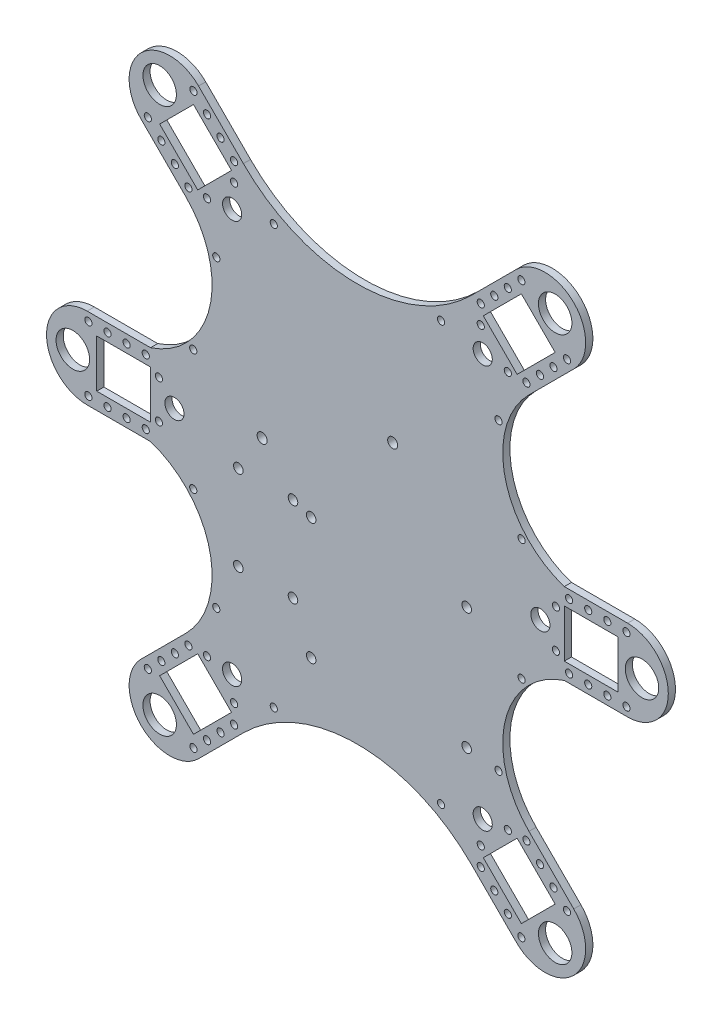
SolidWorks part; units mm, degrees
ref_plane "Płaszczyzna przednia" through (0, 0, 0) normal (0, 0, 1) x (1, 0, 0)
ref_plane "Płaszczyzna górna" through (0, 0, 0) normal (0, 1, 0) x (1, 0, 0)
ref_plane "Płaszczyzna prawa" through (0, 0, 0) normal (1, 0, 0) x (0, 0, -1)
sketch "Model" plane through (0, 0, 0) normal (0, 0, 1) x (1, 0, 0)
  line L0 (2252.0948, 928.366) -> (2233.3565, 947.1043)
  line L1 (2209.3149, 923.0627) -> (2228.0532, 904.3244)
  line L2 (2247.1451, 923.4163) -> (2231.2352, 939.3262)
  line L3 (2233.0029, 909.2741) -> (2247.1451, 923.4163)
  line L4 (2217.093, 925.184) -> (2233.0029, 909.2741)
  line L5 (2231.2352, 939.3262) -> (2217.093, 925.184)
  line L6 (2213.2789, 842.2855) -> (2186.7789, 842.2855)
  line L7 (2186.7789, 808.2855) -> (2213.2789, 808.2855)
  line L8 (2213.2789, 835.2855) -> (2190.7789, 835.2855)
  line L9 (2213.2789, 815.2855) -> (2213.2789, 835.2855)
  line L10 (2190.7789, 815.2855) -> (2213.2789, 815.2855)
  line L11 (2190.7789, 835.2855) -> (2190.7789, 815.2855)
  line L12 (2231.2352, 711.2448) -> (2217.093, 725.3869)
  line L13 (2217.093, 725.3869) -> (2233.0029, 741.2968)
  line L14 (2233.0029, 741.2968) -> (2247.1451, 727.1547)
  line L15 (2247.1451, 727.1547) -> (2231.2352, 711.2448)
  line L16 (2209.3149, 727.5082) -> (2228.0532, 746.2466)
  line L17 (2252.0948, 722.2049) -> (2233.3565, 703.4666)
  line L18 (2347.4886, 722.2049) -> (2366.2269, 703.4666)
  line L19 (2390.2686, 727.5082) -> (2371.5302, 746.2466)
  line L20 (2352.4384, 727.1547) -> (2368.3483, 711.2448)
  line L21 (2366.5805, 741.2968) -> (2352.4384, 727.1547)
  line L22 (2382.4904, 725.3869) -> (2366.5805, 741.2968)
  line L23 (2368.3483, 711.2448) -> (2382.4904, 725.3869)
  line L24 (2408.8046, 835.2855) -> (2408.8046, 815.2855)
  line L25 (2149.0438, 825.2855) -> (2452.6529, 825.2855) construction
  line L26 (2408.8046, 815.2855) -> (2386.3046, 815.2855)
  line L27 (2386.3046, 815.2855) -> (2386.3046, 835.2855)
  line L28 (2386.3046, 835.2855) -> (2408.8046, 835.2855)
  line L29 (2412.8046, 808.2855) -> (2386.3046, 808.2855)
  line L30 (2386.3046, 842.2855) -> (2412.8046, 842.2855)
  line L31 (2368.3483, 939.3262) -> (2382.4904, 925.184)
  line L32 (2382.4904, 925.184) -> (2366.5805, 909.2741)
  line L33 (2366.5805, 909.2741) -> (2352.4384, 923.4163)
  line L34 (2352.4384, 923.4163) -> (2368.3483, 939.3262)
  line L35 (2390.2686, 923.0627) -> (2371.5302, 904.3244)
  line L36 (2347.4886, 928.366) -> (2366.2269, 947.1043)
  line L39 (2201.5792, 877.8504) -> (2238.0005, 869.1768) construction
  line L66 (2299.7917, 657.0048) -> (2299.7917, 965.92) construction
  arc A2 (2209.3149, 727.5082) -> (2233.3565, 703.4666) centre (2221.3357, 715.4874) ccw
  arc A3 (2252.0948, 928.366) -> (2347.4886, 928.366) centre (2299.7917, 976.0629) ccw
  circle A4 centre (2242.5489, 717.6087) radius 1.5
  circle A5 centre (2248.2057, 927.3054) radius 1.5
  circle A6 centre (2248.2057, 919.5272) radius 1.5
  arc A7 (2228.0532, 904.3244) -> (2213.2789, 842.2855) centre (2201.5792, 877.8504) cw
  circle A8 centre (2229.1139, 908.2135) radius 1.5
  circle A9 centre (2223.457, 913.8703) radius 1.5
  circle A10 centre (2217.8001, 919.5272) radius 1.5
  circle A11 centre (2212.1433, 925.184) radius 1.5
  circle A12 centre (2217.093, 939.3262) radius 7
  circle A13 centre (2236.892, 908.2135) radius 1.5
  circle A14 centre (2231.2352, 944.2759) radius 1.5
  circle A15 centre (2236.892, 938.6191) radius 1.5
  circle A16 centre (2242.5489, 932.9622) radius 1.5
  arc A17 (2209.3149, 923.0627) -> (2233.3565, 947.1043) centre (2221.3357, 935.0835) cw
  circle A18 centre (2236.892, 711.9519) radius 1.5
  circle A19 centre (2180.7789, 825.2855) radius 7
  circle A20 centre (2187.2789, 838.7855) radius 1.5
  circle A21 centre (2195.2789, 838.7855) radius 1.5
  circle A22 centre (2203.2789, 838.7855) radius 1.5
  circle A23 centre (2187.2789, 811.7855) radius 1.5
  circle A24 centre (2195.2789, 811.7855) radius 1.5
  circle A25 centre (2203.2789, 811.7855) radius 1.5
  circle A26 centre (2211.2789, 811.7855) radius 1.5
  circle A27 centre (2216.7789, 817.2855) radius 1.5
  circle A28 centre (2211.2789, 838.7855) radius 1.5
  circle A29 centre (2216.7789, 833.2855) radius 1.5
  arc A30 (2186.7789, 808.2855) -> (2186.7789, 842.2855) centre (2186.7789, 825.2855) cw
  circle A31 centre (2231.2352, 706.295) radius 1.5
  circle A32 centre (2236.892, 742.3575) radius 1.5
  circle A33 centre (2217.093, 711.2448) radius 7
  circle A34 centre (2212.1433, 725.3869) radius 1.5
  circle A35 centre (2217.8001, 731.0438) radius 1.5
  circle A36 centre (2223.457, 736.7006) radius 1.5
  circle A37 centre (2229.1139, 742.3575) radius 1.5
  arc A38 (2228.0532, 746.2466) -> (2213.2789, 808.2855) centre (2201.5792, 772.7206) ccw
  circle A39 centre (2248.2057, 731.0438) radius 1.5
  circle A42 centre (2248.2057, 723.2656) radius 1.5
  arc A43 (2252.0948, 722.2049) -> (2347.4886, 722.2049) centre (2299.7917, 674.508) cw
  circle A45 centre (2351.3777, 723.2656) radius 1.5
  circle A48 centre (2351.3777, 731.0438) radius 1.5
  arc A49 (2371.5302, 746.2466) -> (2386.3046, 808.2855) centre (2398.0042, 772.7206) cw
  circle A50 centre (2370.4696, 742.3575) radius 1.5
  circle A51 centre (2376.1264, 736.7006) radius 1.5
  circle A52 centre (2381.7833, 731.0438) radius 1.5
  circle A53 centre (2387.4401, 725.3869) radius 1.5
  circle A54 centre (2382.4904, 711.2448) radius 7
  circle A55 centre (2362.6914, 742.3575) radius 1.5
  circle A56 centre (2368.3483, 706.295) radius 1.5
  arc A57 (2412.8046, 808.2855) -> (2412.8046, 842.2855) centre (2412.8046, 825.2855) ccw
  circle A58 centre (2382.8046, 833.2855) radius 1.5
  circle A59 centre (2388.3046, 838.7855) radius 1.5
  circle A60 centre (2382.8046, 817.2855) radius 1.5
  circle A61 centre (2388.3046, 811.7855) radius 1.5
  circle A62 centre (2396.3046, 811.7855) radius 1.5
  circle A63 centre (2404.3046, 811.7855) radius 1.5
  circle A64 centre (2412.3046, 811.7855) radius 1.5
  circle A65 centre (2396.3046, 838.7855) radius 1.5
  circle A66 centre (2404.3046, 838.7855) radius 1.5
  circle A67 centre (2412.3046, 838.7855) radius 1.5
  circle A68 centre (2418.8046, 825.2855) radius 7
  circle A69 centre (2362.6914, 711.9519) radius 1.5
  arc A70 (2390.2686, 923.0627) -> (2366.2269, 947.1043) centre (2378.2478, 935.0835) ccw
  circle A71 centre (2357.0346, 932.9622) radius 1.5
  circle A72 centre (2362.6914, 938.6191) radius 1.5
  circle A73 centre (2368.3483, 944.2759) radius 1.5
  circle A74 centre (2362.6914, 908.2135) radius 1.5
  circle A75 centre (2382.4904, 939.3262) radius 7
  circle A76 centre (2387.4401, 925.184) radius 1.5
  circle A77 centre (2381.7833, 919.5272) radius 1.5
  circle A78 centre (2376.1264, 913.8703) radius 1.5
  circle A79 centre (2370.4696, 908.2135) radius 1.5
  arc A81 (2371.5302, 904.3244) -> (2386.3046, 842.2855) centre (2398.0042, 877.8504) ccw
  circle A82 centre (2351.3777, 919.5272) radius 1.5
  circle A83 centre (2351.3777, 927.3054) radius 1.5
  circle A84 centre (2357.0346, 717.6087) radius 1.5
  arc A85 (2390.2686, 727.5082) -> (2366.2269, 703.4666) centre (2378.2478, 715.4874) cw
  circle A90 centre (2345.4797, 814.428) radius 2
  circle A91 centre (2345.4797, 763.588) radius 2
  circle A92 centre (2280.4557, 763.588) radius 2
  circle A93 centre (2280.4557, 814.428) radius 2
  circle A94 centre (2259.9437, 832.908) radius 2.1
  circle A95 centre (2314.5437, 858.508) radius 2.1
  circle A96 centre (2247.3913, 909.5204) radius 4
  circle A97 centre (2247.3913, 741.0506) radius 4
  circle A98 centre (2223.2789, 825.2855) radius 4
  circle A99 centre (2352.1921, 741.0506) radius 4
  circle A100 centre (2376.3046, 825.2855) radius 4
  circle A101 centre (2352.1921, 909.5204) radius 4
  circle A102 centre (2272.8517, 781.408) radius 2
  circle A103 centre (2249.9917, 781.408) radius 2
  circle A104 centre (2272.8517, 816.968) radius 2
  circle A105 centre (2249.9917, 816.968) radius 2
  point P3 (2252.0948, 928.366)
  point P6 (2299.7917, 825.2855)
  point P118 (2299.7917, 825.2855)
  dimension "D6" = 10
  dimension "D5" = 10
extrude "Dodanie-wyciągnięcie1" add sketch "Model" along normal blind 3
ref_point "Punkt1"
ref_point "Punkt2"
ref_point "Punkt3"
ref_point "Punkt4"
ref_plane "Płaszczyzna1" through (2299.7917, 0, 0) normal (1, 0, 0) x (0, 0, -1)
ref_plane "Płaszczyzna2" through (0, 825.2855, 0) normal (0, -1, 0) x (-1, 0, 0)
sketch "Szkic1" plane through (0, 0, 3) normal (0, 0, 1) x (1, 0, 0)
  circle A0 centre (2334.7607, 737.7613) radius 1.5
  circle A1 centre (2358.8023, 761.8029) radius 1.5
  circle A2 centre (2368.4429, 800.0114) radius 1.5
  circle A3 centre (2368.4429, 850.5595) radius 1.5
  circle A4 centre (2358.8023, 888.768) radius 1.5
  circle A5 centre (2334.7607, 912.8097) radius 1.5
  circle A6 centre (2264.8227, 912.8097) radius 1.5
  circle A7 centre (2240.7811, 888.768) radius 1.5
  circle A8 centre (2231.1406, 850.5595) radius 1.5
  circle A9 centre (2231.1406, 800.0114) radius 1.5
  circle A10 centre (2240.7811, 761.8029) radius 1.5
  circle A11 centre (2264.8227, 737.7613) radius 1.5
extrude "Wytnij-wyciągnięcie1" cut sketch "Szkic1" against normal through all
ref_point "Punkt5"
